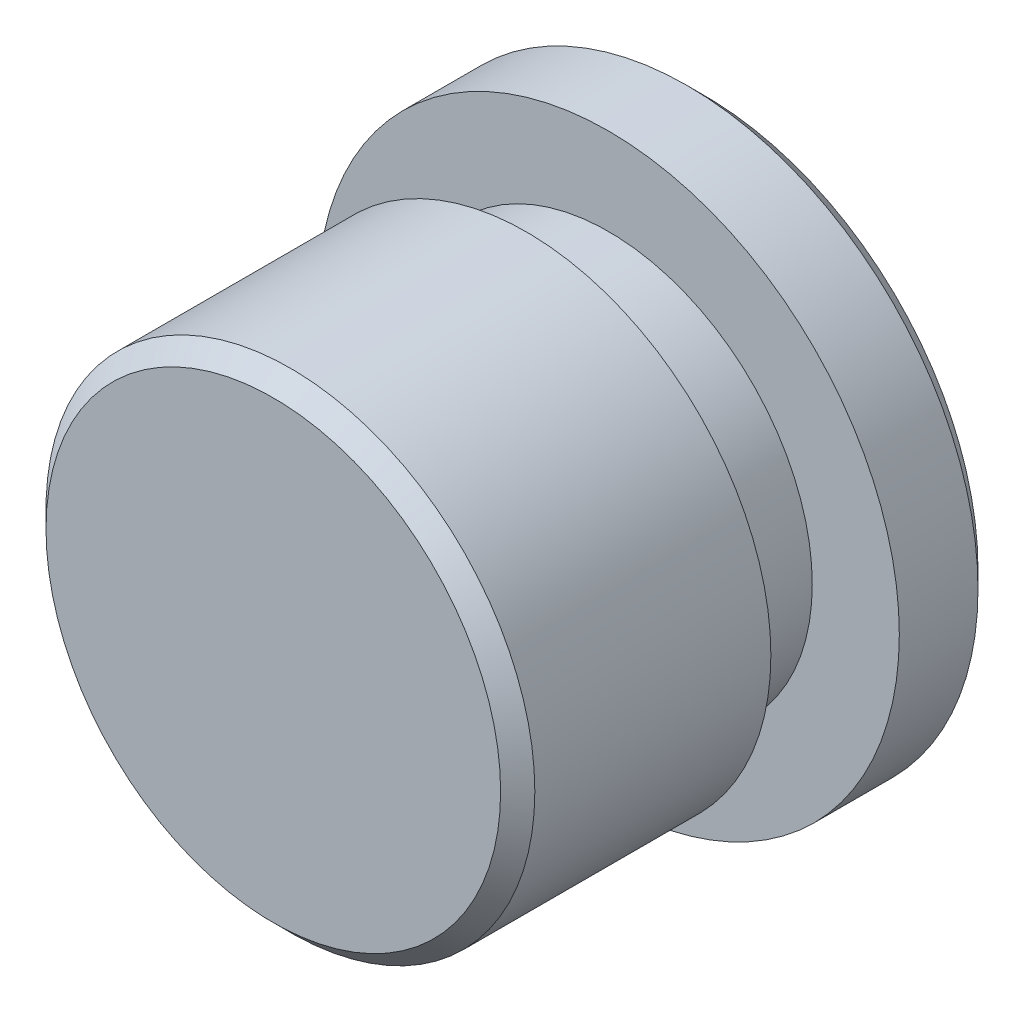
SolidWorks part; units mm, degrees
ref_plane "前视基准面" through (0, 0, 0) normal (0, 0, 1) x (1, 0, 0)
ref_plane "上视基准面" through (0, 0, 0) normal (0, 1, 0) x (1, 0, 0)
ref_plane "右视基准面" through (0, 0, 0) normal (1, 0, 0) x (0, 0, -1)
sketch "草图1" plane through (0, 0, 0) normal (0, 0, 1) x (1, 0, 0)
  circle A0 centre (0, 0) radius 8.5
  dimension "D1" = 17
extrude "拉伸1" add sketch "草图1" along normal blind 2.8
sketch "草图2" plane through (0, 0, 2.8) normal (0, 0, 1) x (1, 0, 0)
  circle A0 centre (0, 0) radius 5.955
  dimension "D1" = 11.91
extrude "拉伸2" add sketch "草图2" along normal blind 2.4
sketch "草图3" plane through (0, 0, 5.2) normal (0, 0, 1) x (1, 0, 0)
  circle A0 centre (0, 0) radius 7.145
  dimension "D1" = 14.29
extrude "拉伸3" add sketch "草图3" along normal blind 7.4
chamfer "倒角1" distance 0.5 angle 45 1 edges at (7.145, 0, 12.6)
chamfer "倒角2" distance 0.5 angle 45 1 edges at (8.5, 0, 0)
sketch "草图4" plane through (0, 0, 0) normal (0, 0, -1) x (-1, 0, 0)
  line L1 (2.2581, -2.627) -> (3.4041, 0.6421)
  line L2 (3.4041, 0.6421) -> (1.146, 3.2691)
  line L3 (1.146, 3.2691) -> (-2.2581, 2.627)
  line L4 (-2.2581, 2.627) -> (-3.4041, -0.6421)
  line L5 (-3.4041, -0.6421) -> (-1.146, -3.2691)
  line L6 (-1.146, -3.2691) -> (2.2581, -2.627)
  circle A0 centre (0, 0) radius 3 construction
  dimension "D1" = 6
extrude "切除-拉伸1" cut sketch "草图4" against normal blind 5.2
sketch "草图5" plane through (0, 0, 0) normal (0, 0, -1) x (-1, 0, 0)
  circle A0 centre (0, 0) radius 3.4641
extrude "切除-拉伸2" cut sketch "草图5" against normal blind 0.5 draft 37
ref_plane "MD_PLANE" through (0, 0, 2.8) normal (0, 0, 1) x (1, 0, 0)
ref_axis "MD_AXIS1" through (0, 0, 12.1) along (0, 0, -1)
